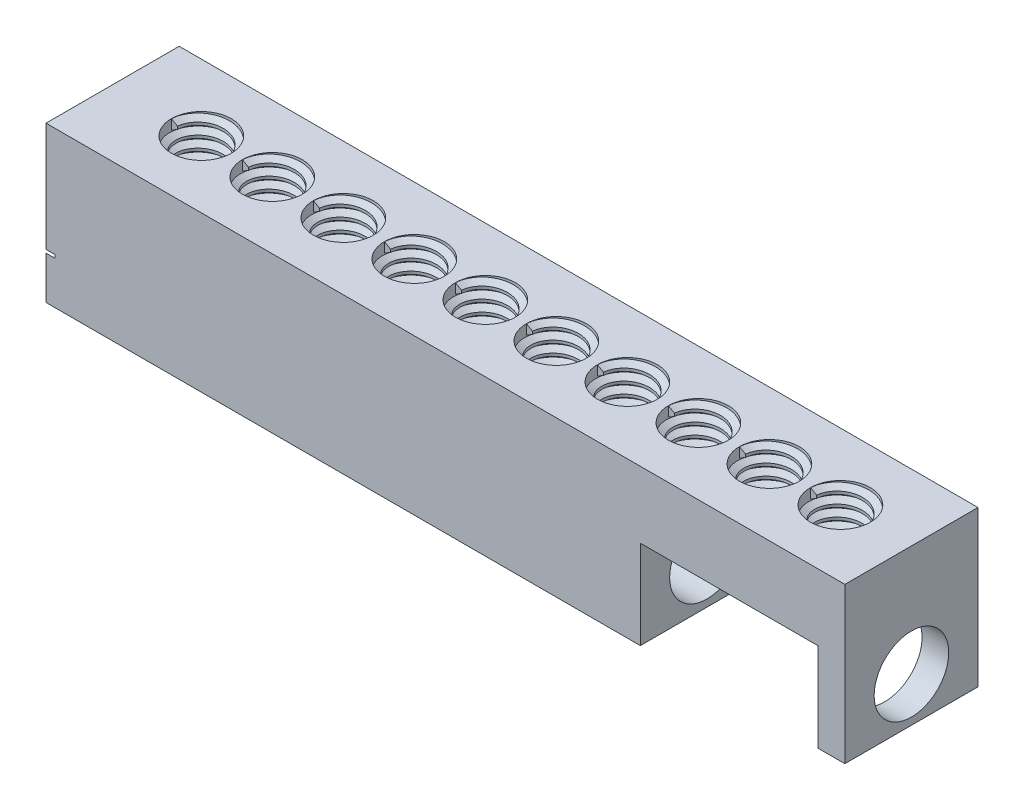
SolidWorks part; units mm, degrees
ref_plane "Front Plane" through (0, 0, 0) normal (0, 0, 1) x (1, 0, 0)
ref_plane "Top Plane" through (0, 0, 0) normal (0, 1, 0) x (1, 0, 0)
ref_plane "Right Plane" through (0, 0, 0) normal (1, 0, 0) x (0, 0, -1)
sketch "Эскиз1" plane through (0, 0, 0) normal (0, 1, 0) x (1, 0, 0)
  line L1 (0, 0) -> (90, 0)
  line L2 (0, 0) -> (0, -15)
  line L3 (0, -15) -> (90, -15)
  line L4 (90, 0) -> (90, -15)
  dimension "D1" = 15
  dimension "D2" = 90
extrude "Бобышка-Вытянуть1" add sketch "Эскиз1" along normal blind 17.5
sketch "Эскиз2" plane through (0, 0, 0) normal (-1, 0, 0) x (0, 0, 1)
  line L0 (0, 0) -> (15, 0) construction
  circle A0 centre (7.5, 5) radius 4.2
  dimension "D1" = 5
extrude "Вырез-Вытянуть1" cut sketch "Эскиз2" against normal through all
sketch "Эскиз3" plane through (0, 0, 0) normal (0, -1, 0) x (1, 0, 0)
  line L0 (0, 15) -> (90, 15) construction
  line L1 (87, 15) -> (66.96, 15)
  line L2 (87, 15) -> (87, 0)
  line L3 (87, 0) -> (66.96, 0)
  line L4 (66.96, 15) -> (66.96, 0)
  line L5 (90, 15) -> (90, 0) construction
  dimension "D1" = 20.04
  dimension "D2" = 3
extrude "Вырез-Вытянуть2" cut sketch "Эскиз3" against normal blind 10
sketch "Эскиз4" plane through (0, 17.5, 0) normal (0, 1, 0) x (1, 0, 0)
  line L0 (90, -15) -> (90, 0) construction
  circle A0 centre (82, -7.5) radius 3.375
  dimension "D2" = 6.75
  dimension "D1" = 8
extrude "Вырез-Вытянуть3" cut sketch "Эскиз4" against normal blind 7.5
thread "Резьба1" pitch 1.27 start angle 0, offset 0, length 6.2, pitch 1.27, diameter 6.75
ref_plane "Плоскость2" through (78.625, 17.5, 7.5) normal (0, 0, 1) x (-1, 0, 0)
sketch "Профиль резьбы2" plane through (78.625, 17.5, 7.5) normal (0, 0, 1) x (-1, 0, 0)
  line L0 (0, 0) -> (0, 1.27) construction
  line L11 (0, 0) -> (0, 1.1112)
  line L12 (0, 1.1112) -> (-0.6874, 0.7144)
  line L13 (-0.6874, 0.7144) -> (-0.6874, 0.3969)
  line L15 (-0.6874, 0.3969) -> (0, 0)
  line L17 (-0.6874, 0.5556) -> (0, 0.5556) construction
  point P2 (0, 0)
  dimension "Pitch" = 1.27
  dimension "Profile_Angle" = 60
  dimension "Profile_Land" = 0.3175
  dimension "Profile_Height" = 0.6874
pattern_linear "Линейный массив1" count 10 spacing 8 along (1, 0, 0) of "Вырез-Вытянуть3", "Резьба1"
sketch "Эскиз12" plane through (0, 0, 0) normal (-1, 0, 0) x (0, 0, 1)
  line L1 (-0.1, 5) -> (3.7, -1.5818)
  line L2 (3.7, -1.5818) -> (11.3, -1.5818)
  line L3 (11.3, -1.5818) -> (15.1, 5)
  line L4 (15.1, 5) -> (11.3, 11.5818)
  line L5 (11.3, 11.5818) -> (3.7, 11.5818)
  line L6 (3.7, 11.5818) -> (-0.1, 5)
  circle A0 centre (7.5, 5) radius 6.5818 construction
  dimension "D1" = 15.2
extrude "Вырез-Вытянуть4" cut sketch "Эскиз12" against normal blind 1
